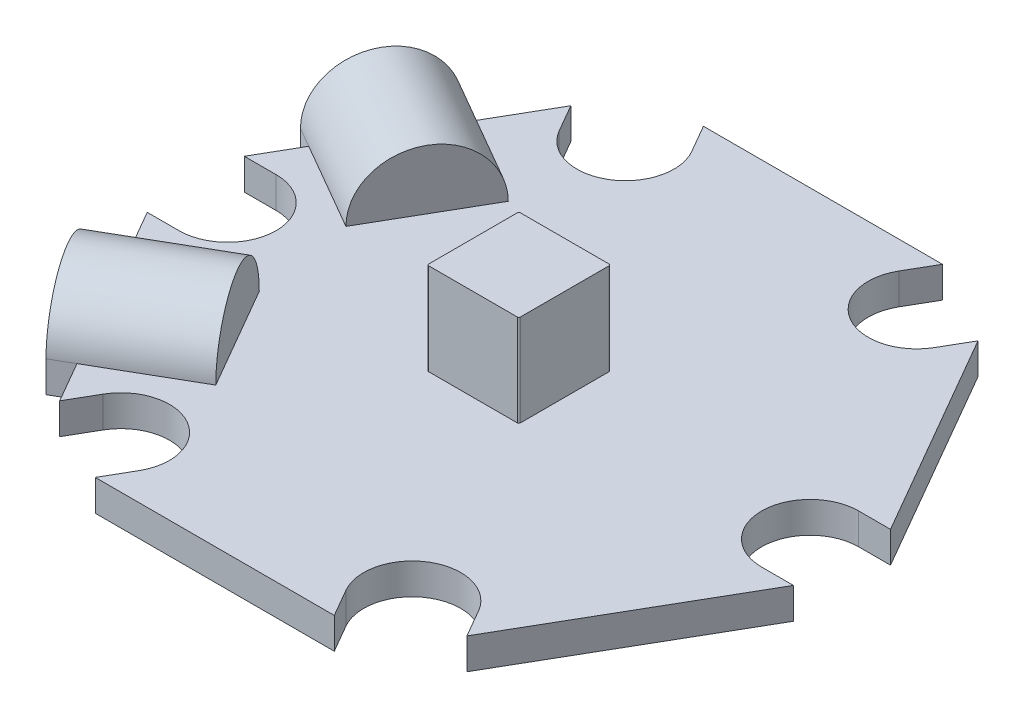
SolidWorks part; units mm, degrees
ref_plane "Front Plane" through (0, 0, 0) normal (0, 0, 1) x (1, 0, 0)
ref_plane "Top Plane" through (0, 0, 0) normal (0, 1, 0) x (1, 0, 0)
ref_plane "Right Plane" through (0, 0, 0) normal (1, 0, 0) x (0, 0, -1)
sketch "Sketch1" plane through (0, 0, 0) normal (0, 1, 0) x (1, 0, 0)
  line L7 (5.7412, 9.9441) -> (-5.7412, 9.9441)
  line L8 (-5.7412, 9.9441) -> (-11.4825, 0)
  line L9 (-11.4825, 0) -> (-5.7412, -9.9441)
  line L10 (-5.7412, -9.9441) -> (5.7412, -9.9441)
  line L11 (5.7412, -9.9441) -> (11.4825, 0)
  line L12 (11.4825, 0) -> (5.7412, 9.9441)
  circle A1 centre (0, 0) radius 9.9441 construction
extrude "Boss-Extrude1" add sketch "Sketch1" along normal blind 1.016
sketch "Sketch2" plane through (0, 1.016, 0) normal (0, 1, 0) x (1, 0, 0)
  line L6 (9.525, 1.5875) -> (13.1378, 1.5875)
  line L12 (9.525, -1.5875) -> (13.1378, -1.5875)
  line L13 (13.1378, 1.5875) -> (13.1378, -1.5875)
  arc A1 (9.525, 1.5875) -> (9.525, -1.5875) centre (9.525, 0) ccw
  dimension "D1" = 9.525
extrude "Cut-Extrude1" cut sketch "Sketch2" against normal blind 1.016
ref_axis "Axis1" through (0, 4.2168, 0) along (0, -1, 0)
pattern_circular "CirPattern1" count 6 every 60 about axis through (0, 4.2168, 0) along (0, -1, 0) of "Cut-Extrude1"
sketch "Sketch3" plane through (0, 1.016, 0) normal (0, 1, 0) x (1, 0, 0)
  line L1 (-1.5, -1.5) -> (-1.5, 1.5)
  line L2 (-1.5, -1.5) -> (1.5, -1.5)
  line L3 (-1.5, 1.5) -> (1.5, 1.5)
  line L4 (1.5, -1.5) -> (1.5, 1.5)
  line L6 (-1.5, 1.5) -> (-0.0012, 0.0012) construction
  point P9 (0, 0)
  dimension "D1" = 3
  dimension "D2" = 3
extrude "Boss-Extrude2" add sketch "Sketch3" along normal blind 3
fillet "Fillet1" radius 0.0508 1 edges at (1.5, 2.516, 1.5)
fillet "Fillet2" radius 0.0508 1 edges at (-1.5, 2.516, -1.5)
fillet "Fillet3" radius 0.0508 1 edges at (1.5, 2.516, -1.5)
fillet "Fillet4" radius 0.0508 1 edges at (-1.5, 2.516, 1.5)
sketch "Sketch4" plane through (0, 1.016, 0) normal (0, 1, 0) x (1, 0, 0)
  line L0 (-8.4528, -3.1242) -> (-6.5097, -6.4897)
  line L1 (-8.4528, -3.1242) -> (-6.4951, -1.9939)
  line L2 (-6.5097, -6.4897) -> (-4.552, -5.3594)
  line L3 (-6.4951, -1.9939) -> (-4.552, -5.3594)
  line L4 (-8.4528, -3.1242) -> (-4.552, -5.3594) construction
  line L5 (-6.5097, -6.4897) -> (-6.4951, -1.9939) construction
  line L11 (-1.5, 1.4492) -> (-1.5, -1.4492) construction
  point P1 (-6.5024, -4.2418)
  point P13 (-1.5, 0)
  dimension "D1" = 3.8862
  dimension "D2" = 2.2606
  dimension "D3" = 6.5024
  dimension "D4" = 4.2418
ref_plane "Plane1" through (-5.7347, 0, 3.3109) normal (-0.866, 0, 0.5) x (0.5, 0, 0.866)
sketch "Sketch5" plane through (-5.7347, 0, 3.3109) normal (-0.866, 0, 0.5) x (0.5, 0, 0.866)
  line L0 (-1.5208, 1.016) -> (2.3654, 1.016) construction
  line L1 (-1.5208, 1.016) -> (2.3654, 1.016)
  arc A0 (-1.5208, 1.016) -> (2.3654, 1.016) centre (0.4223, 1.016) cw
extrude "Boss-Extrude3" add sketch "Sketch5" along normal blind 4.064 contours A0 L1 region at (-5.5235, 1.8407, 3.6766)
pattern_circular "CirPattern2" count 2 every 60 about axis through (0, 4.2168, 0) along (0, -1, 0) of "Boss-Extrude3"
sketch "Sketch7" plane through (0, 1.016, 0) normal (0, -1, 0) x (1, 0, 0)
  line L4 (-10.0146, 4.0259) -> (-9.3722, 3.655)
  line L5 (-9.3722, 3.655) -> (-7.4291, 7.0206)
  line L6 (-7.4291, 7.0206) -> (-8.0715, 7.3914)
  line L7 (-8.0715, 7.3914) -> (-10.0146, 4.0259)
  line L8 (-10.0146, 4.0259) -> (-9.3722, 3.655)
  line L9 (-9.3722, 3.655) -> (-7.4291, 7.0206)
  line L10 (-7.4291, 7.0206) -> (-8.0715, 7.3914)
  line L11 (-8.0715, 7.3914) -> (-10.0146, 4.0259)
  dimension "D1" = 0
extrude "Boss-Extrude4" add sketch "Sketch7" along normal up to surface (1.016 mm away) up to face at (0, 0, 0)
sketch "Sketch8" plane through (0, 1.016, 0) normal (0, -1, 0) x (1, 0, 0)
  line L4 (-8.4938, -6.66) -> (-7.8514, -6.2891)
  line L5 (-7.8514, -6.2891) -> (-9.7945, -2.9235)
  line L6 (-9.7945, -2.9235) -> (-10.4369, -3.2944)
  line L7 (-10.4369, -3.2944) -> (-8.4938, -6.66)
  line L8 (-8.4938, -6.66) -> (-7.8514, -6.2891)
  line L9 (-7.8514, -6.2891) -> (-9.7945, -2.9235)
  line L10 (-9.7945, -2.9235) -> (-10.4369, -3.2944)
  line L11 (-10.4369, -3.2944) -> (-8.4938, -6.66)
  dimension "D1" = 0
extrude "Boss-Extrude5" add sketch "Sketch8" along normal up to surface (1.016 mm away) up to face at (-1.246, 0, 0.789)
